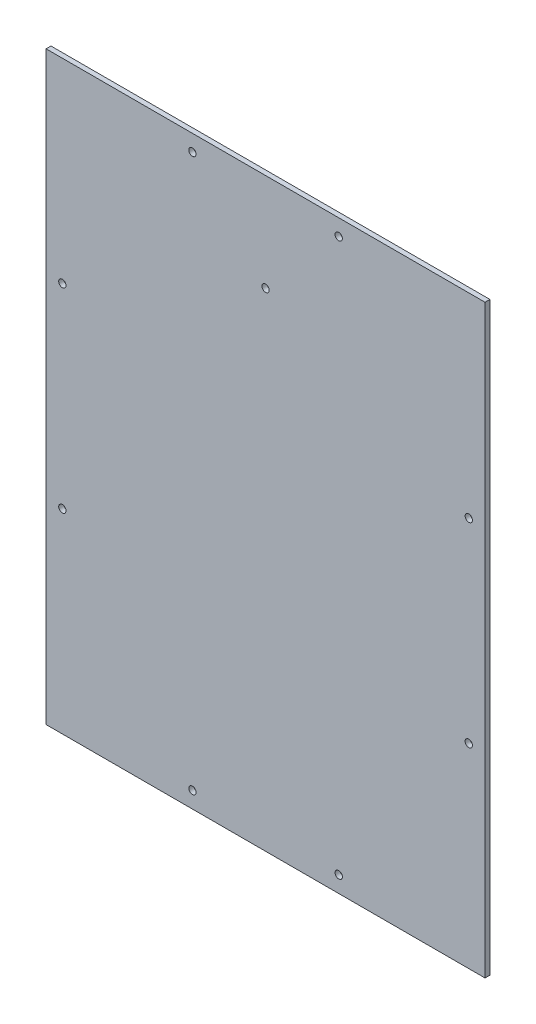
SolidWorks part; units mm, degrees
ref_plane "Спереди" through (0, 0, 0) normal (0, 0, 1) x (1, 0, 0)
ref_plane "Сверху" through (0, 0, 0) normal (0, 1, 0) x (1, 0, 0)
ref_plane "Справа" through (0, 0, 0) normal (1, 0, 0) x (0, 0, -1)
sketch "Эскиз1" plane through (0, 0, 0) normal (0, 0, 1) x (1, 0, 0)
  line L0 (0, 0) -> (270, 0)
  line L1 (0, 0) -> (0, 360)
  line L2 (270, 0) -> (270, 360)
  line L3 (0, 360) -> (270, 360)
  line L4 (10, 350) -> (260, 350) construction
  line L5 (10, 350) -> (10, 10) construction
  line L6 (260, 350) -> (260, 10) construction
  line L7 (10, 10) -> (260, 10) construction
  line L8 (90, 350) -> (90, 10) construction
  line L9 (180, 350) -> (180, 10) construction
  line L10 (10, 240) -> (260, 240) construction
  line L11 (10, 120) -> (260, 120) construction
  line L12 (135, 350) -> (135, 10) construction
  line L13 (0, 0) -> (20, 0) construction
  line L14 (0, 0) -> (0, 20) construction
  line L15 (20, 0) -> (20, 20) construction
  line L16 (0, 20) -> (20, 20) construction
  line L17 (270, 360) -> (250, 360) construction
  line L18 (270, 360) -> (270, 340) construction
  line L19 (250, 360) -> (250, 340) construction
  line L20 (270, 340) -> (250, 340) construction
  circle A0 centre (90, 350) radius 2.25
  circle A1 centre (180, 350) radius 2.25
  circle A2 centre (10, 240) radius 2.25
  circle A3 centre (10, 120) radius 2.25
  circle A4 centre (260, 240) radius 2.25
  circle A5 centre (260, 120) radius 2.25
  circle A6 centre (90, 10) radius 2.25
  circle A7 centre (180, 10) radius 2.25
  dimension "D9" = 4.5
  dimension "D10" = 4.5
  dimension "D11" = 4.5
  dimension "D12" = 120
  dimension "D13" = 4.5
  dimension "D14" = 120
  dimension "D15" = 4.5
  dimension "D16" = 4.5
  dimension "D20" = 4.5
  dimension "D17" = 4.5
  dimension "D1" = 360
  dimension "D2" = 270
  dimension "D3" = 90
  dimension "D4" = 10
  dimension "D5" = 10
  dimension "D6" = 10
  dimension "D7" = 10
  dimension "D8" = 90
  dimension "D18" = 20
  dimension "D19" = 20
  dimension "D28" = 20
  dimension "D29" = 20
extrude "Бобышка-Вытянуть1" add sketch "Эскиз1" along normal blind 3
sketch "Sketch1" plane through (0, 0, 0) normal (0, 0, -1) x (-1, 0, 0)
  line L0 (-250, 290) -> (-20, 290) construction
  line L1 (-250, 290) -> (-20, 290) construction
  line L2 (-250, 310) -> (-20, 310) construction
  line L3 (-250, 310) -> (-20, 310) construction
  line L4 (-135, 310) -> (-135, 290) construction
  circle A0 centre (-135, 300) radius 2.25
  dimension "D1" = 4.5
extrude "Cut-Extrude1" cut sketch "Sketch1" against normal through all
